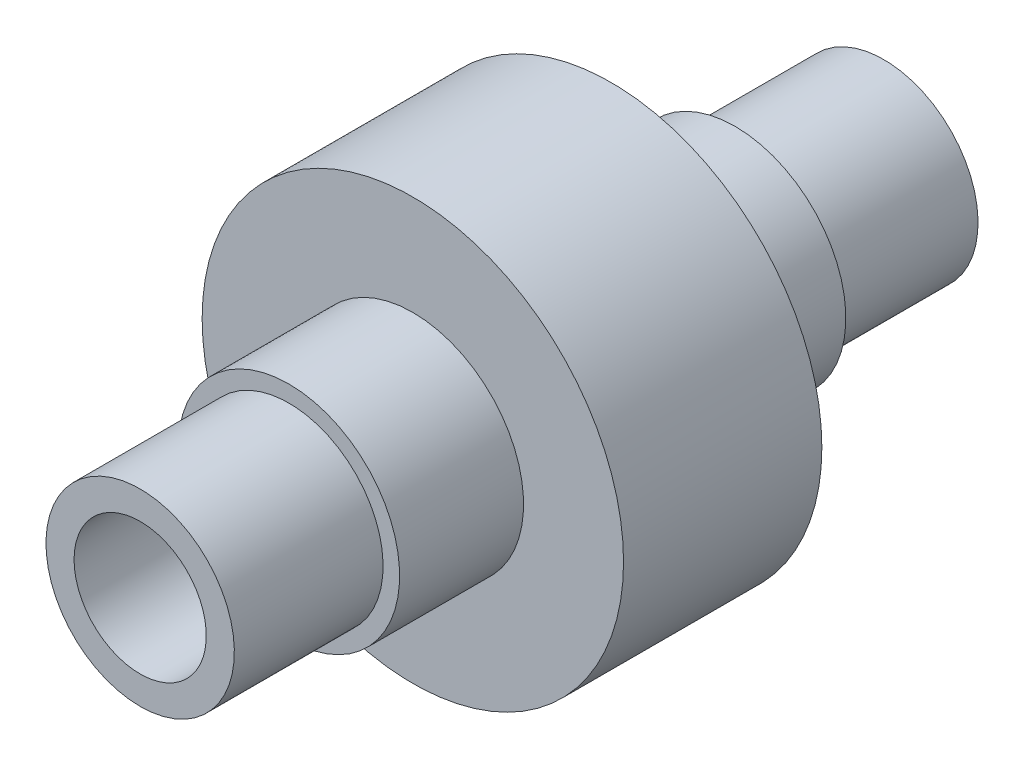
SolidWorks part; units mm, degrees
ref_plane "前视基准面" through (0, 0, 0) normal (0, 0, 1) x (1, 0, 0)
ref_plane "上视基准面" through (0, 0, 0) normal (0, 1, 0) x (1, 0, 0)
ref_plane "右视基准面" through (0, 0, 0) normal (1, 0, 0) x (0, 0, -1)
sketch "草图1" plane through (0, 0, 0) normal (1, 0, 0) x (0, 0, -1)
  line L0 (-21.2214, 0) -> (28.1258, 0) construction
  line L1 (-22.5, 0) -> (-22.5, 5.7)
  line L2 (-22.5, 5.7) -> (-13.5, 5.7)
  line L3 (-13.5, 5.7) -> (-13.5, 6.7) construction
  line L4 (-11.3555, 6.7) -> (-6, 6.7)
  line L5 (-6, 6.7) -> (-6, 14)
  line L6 (-6, 14) -> (6, 14)
  line L7 (0, 14) -> (0, 0) construction
  line L8 (6, 6.7) -> (6, 14)
  line L9 (11.3555, 6.7) -> (6, 6.7)
  line L10 (13.5, 5.7) -> (13.5, 6.7) construction
  line L11 (22.5, 5.7) -> (13.5, 5.7)
  line L12 (22.5, 0) -> (22.5, 5.7)
  line L13 (-22.5, 0) -> (22.5, 0)
  line L15 (-13.5, 6.7) -> (-11.3555, 6.7) construction
  line L17 (13.5, 6.7) -> (11.3555, 6.7) construction
  line L18 (11.3555, 6.7) -> (13.5, 6.7)
  line L19 (13.5, 6.7) -> (13.5, 5.7)
  line L20 (-11.3555, 6.7) -> (-13.5, 6.7)
  line L21 (-13.5, 6.7) -> (-13.5, 5.7)
  dimension "D1" = 5.7
  dimension "D2" = 12
  dimension "D3" = 14
  dimension "D4" = 9
  dimension "D5" = 7.5
  dimension "D6" = 6.7
  dimension "D7" = 45
revolve "旋转1" add sketch "草图1" angle 360 about L13
sketch "草图2" plane through (0, 0, 6) normal (0, 0, 1) x (1, 0, 0)
  line L0 (0, 0) -> (0, 10.5) construction
  circle A0 centre (0, 0) radius 10.5 construction
  circle A1 centre (0, 10.5) radius 1.5
  circle A2 centre (0, 0) radius 10.5 construction
  circle A3 centre (10.5, 0) radius 1.5
  circle A4 centre (0, 0) radius 10.5 construction
  circle A5 centre (0, -10.5) radius 1.5
  circle A6 centre (0, 0) radius 10.5 construction
  circle A7 centre (-10.5, 0) radius 1.5
  dimension "D1" = 21
  dimension "D2" = 3
  dimension "D3" = 4
extrude "切除-拉伸1" cut sketch "草图2" against normal through all
sketch "草图4" plane through (0, 0, -6) normal (0, 0, -1) x (-1, 0, 0)
  circle A0 centre (0, 0) radius 12.75
  circle A1 centre (0, 0) radius 14 construction
  circle A2 centre (0, 0) radius 14
  dimension "D1" = 25.5
extrude "切除-拉伸4" cut sketch "草图4" against normal through all
sketch "草图5" plane through (0, 0, -6) normal (0, 0, -1) x (-1, 0, 0)
  line L0 (-9.2687, 3.6181) -> (-8.332, 3.2525)
  line L1 (-3.6181, 9.2687) -> (-3.2525, 8.332)
  line L8 (3.6181, 9.2687) -> (3.2525, 8.332)
  line L9 (9.2687, 3.6181) -> (8.332, 3.2525)
  line L10 (9.2687, -3.6181) -> (8.332, -3.2525)
  line L11 (3.6181, -9.2687) -> (3.2525, -8.332)
  line L12 (-3.6181, -9.2687) -> (-3.2525, -8.332)
  line L13 (-9.2687, -3.6181) -> (-8.332, -3.2525)
  circle A2 centre (-10.5, 0) radius 1.5 construction
  circle A4 centre (0, 10.5) radius 1.5 construction
  arc A6 (-3.7191, 7.083) -> (-7.083, 3.7191) centre (0, 0) ccw
  arc A7 (-5.0046, 9.7956) -> (-9.7956, 5.0046) centre (0, 0) ccw
  arc A14 (-8.332, 3.2525) -> (-7.083, 3.7191) centre (-7.9683, 4.184) ccw
  arc A15 (-9.2687, 3.6181) -> (-9.7956, 5.0046) centre (-8.9051, 4.5497) cw
  arc A16 (-3.2525, 8.332) -> (-3.7191, 7.083) centre (-4.184, 7.9683) cw
  arc A17 (-3.6181, 9.2687) -> (-5.0046, 9.7956) centre (-4.5497, 8.9051) ccw
  arc A18 (3.6181, 9.2687) -> (5.0046, 9.7956) centre (4.5497, 8.9051) cw
  arc A19 (3.2525, 8.332) -> (3.7191, 7.083) centre (4.184, 7.9683) ccw
  arc A20 (7.083, 3.7191) -> (3.7191, 7.083) centre (0, 0) ccw
  arc A21 (8.332, 3.2525) -> (7.083, 3.7191) centre (7.9683, 4.184) cw
  arc A22 (9.2687, 3.6181) -> (9.7956, 5.0046) centre (8.9051, 4.5497) ccw
  arc A23 (9.7956, 5.0046) -> (5.0046, 9.7956) centre (0, 0) ccw
  arc A24 (9.2687, -3.6181) -> (9.7956, -5.0046) centre (8.9051, -4.5497) cw
  arc A25 (8.332, -3.2525) -> (7.083, -3.7191) centre (7.9683, -4.184) ccw
  arc A26 (3.7191, -7.083) -> (7.083, -3.7191) centre (0, 0) ccw
  arc A27 (3.2525, -8.332) -> (3.7191, -7.083) centre (4.184, -7.9683) cw
  arc A28 (3.6181, -9.2687) -> (5.0046, -9.7956) centre (4.5497, -8.9051) ccw
  arc A29 (5.0046, -9.7956) -> (9.7956, -5.0046) centre (0, 0) ccw
  arc A30 (-3.6181, -9.2687) -> (-5.0046, -9.7956) centre (-4.5497, -8.9051) cw
  arc A31 (-3.2525, -8.332) -> (-3.7191, -7.083) centre (-4.184, -7.9683) ccw
  arc A32 (-7.083, -3.7191) -> (-3.7191, -7.083) centre (0, 0) ccw
  arc A33 (-8.332, -3.2525) -> (-7.083, -3.7191) centre (-7.9683, -4.184) cw
  arc A34 (-9.2687, -3.6181) -> (-9.7956, -5.0046) centre (-8.9051, -4.5497) ccw
  arc A35 (-9.7956, -5.0046) -> (-5.0046, -9.7956) centre (0, 0) ccw
  point P23 (0, 0)
  point P25 (0, 0)
  point P27 (-10.247, 4)
  point P32 (-4, 10.247)
  point P44 (0, 0)
  point P57 (0, 0)
  point P63 (0, 0)
  dimension "D3" = 11
  dimension "D4" = 8
  dimension "D6" = 1
  dimension "D1" = 4
  dimension "D2" = 4
extrude "切除-拉伸5" cut sketch "草图5" against normal through all
sketch "草图6" plane through (0, 0, -22.5) normal (0, 0, -1) x (-1, 0, 0)
  circle A0 centre (0, 0) radius 4
  dimension "D1" = 8
extrude "切除-拉伸6" cut sketch "草图6" against normal through all
sketch "草图7" plane through (0, 0, -6) normal (0, 0, -1) x (-1, 0, 0)
  circle A0 centre (0, 0) radius 6.7 construction
  circle A1 centre (0, 0) radius 12.75
  circle A2 centre (0, 0) radius 12.75
  circle A3 centre (0, 0) radius 6.7
  dimension "D1" = 0
extrude "凸台-拉伸1" add sketch "草图7" against normal up to surface (12 mm away) up to face at (0, -6.7, 6)
move or copy body "实体-移动/复制1" [suppressed] bodies to move or copy 113
